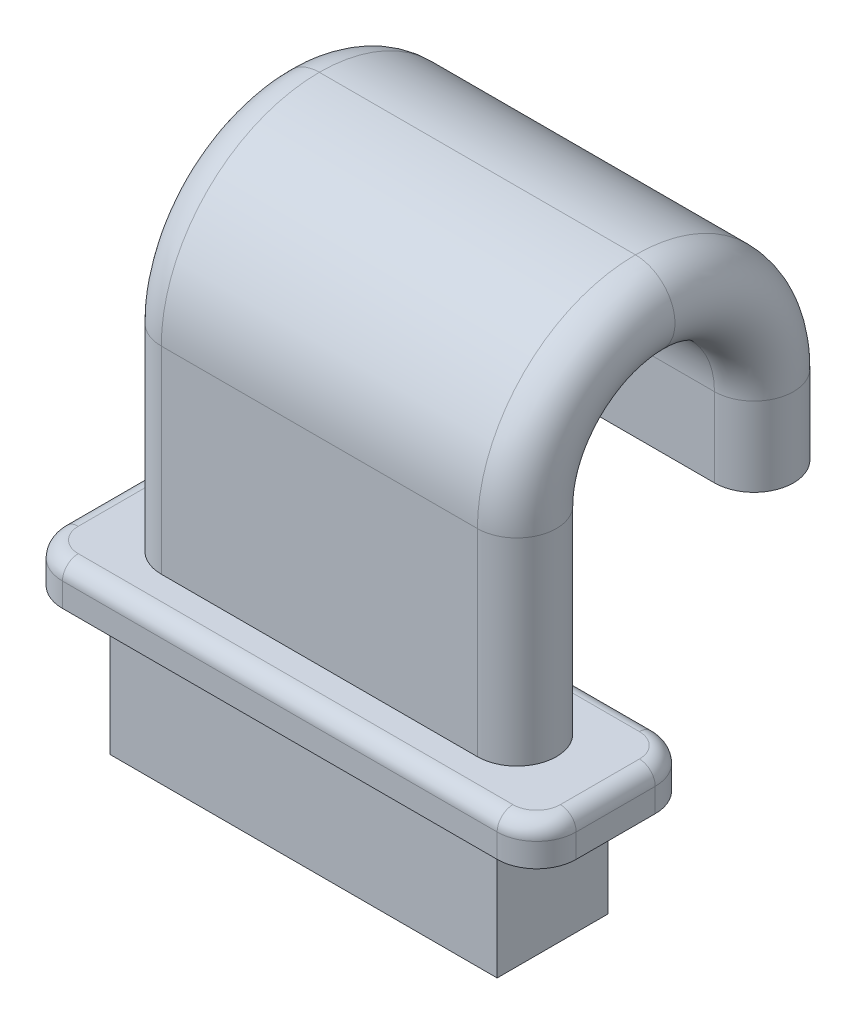
SolidWorks part; units mm, degrees
ref_plane "Front Plane" through (0, 0, 0) normal (0, 0, 1) x (1, 0, 0)
ref_plane "Top Plane" through (0, 0, 0) normal (0, 1, 0) x (1, 0, 0)
ref_plane "Right Plane" through (0, 0, 0) normal (1, 0, 0) x (0, 0, -1)
sketch "Sketch1" plane through (0, 0, 0) normal (1, 0, 0) x (0, 0, -1)
  line L0 (0, 0) -> (0, 25)
  line L2 (30, 25) -> (30, 15)
  arc A0 (0, 25) -> (15, 40) centre (15, 25) cw
  arc A1 (15, 40) -> (30, 25) centre (15, 25) cw
  point P2 (0, 0)
  point P8 (0, 40)
  point P11 (39.9467, 37.9361)
  point P12 (0, 0)
  point P13 (0, 0)
  point P14 (0, 0)
  point P15 (0, 0)
  point P16 (0, 0)
  dimension "D4" = 15
  dimension "D5" = 15
  dimension "D1" = 40
  dimension "D2" = 40
  dimension "D3" = 25
sketch "Sketch2" plane through (0, 0, 0) normal (0, 1, 0) x (1, 0, 0)
  line L0 (0, 0) -> (-40, 0) construction
  line L1 (0, -5) -> (-40, -5)
  line L2 (0, 5) -> (-40, 5)
  arc A1 (0, -5) -> (0, 5) centre (0, 0) ccw
  arc A2 (-40, 5) -> (-40, -5) centre (-40, 0) ccw
  point P2 (-20, 0)
  dimension "D1" = 5
  dimension "D2" = 40
sweep "Sweep1" add profiles "Sketch2" path "Sketch1"
sketch "Sketch3" plane through (0, 0, 0) normal (0, -1, 0) x (1, 0, 0)
  line L0 (5, 0) -> (-45, 0) construction
  line L1 (7.5, -10) -> (-47.5, -10)
  line L2 (12.5, -5) -> (12.5, 5)
  line L3 (7.5, 10) -> (-47.5, 10)
  line L4 (-52.5, -5) -> (-52.5, 5)
  line L5 (-20, -5) -> (-20, 5) construction
  line L6 (0, -5) -> (-40, -5) construction
  line L7 (-40, 5) -> (0, 5) construction
  arc A0 (0, -5) -> (0, 5) centre (0, 0) ccw construction
  arc A1 (-40, 5) -> (-40, -5) centre (-40, 0) ccw construction
  arc A2 (-47.5, -10) -> (-52.5, -5) centre (-47.5, -5) cw
  arc A3 (-47.5, 10) -> (-52.5, 5) centre (-47.5, 5) ccw
  arc A4 (12.5, 5) -> (7.5, 10) centre (7.5, 5) ccw
  arc A5 (7.5, -10) -> (12.5, -5) centre (7.5, -5) ccw
  point P18 (0, 0)
  point P19 (-20, -5)
  point P24 (-52.5, 10)
  point P27 (12.5, 10)
  dimension "D4" = 5
  dimension "D5" = 5
  dimension "D6" = 5
  dimension "D7" = 5
  dimension "D1" = 32.5
  dimension "D2" = 65
  dimension "D3" = 20
extrude "Boss-Extrude1" add sketch "Sketch3" along normal blind 5
fillet "Fillet1" radius 2 8 edges at (11.0355, 0, 8.5355) (12.5, 0, 0) (11.0355, 0, -8.5355) (-20, 0, -10) (-51.0355, 0, -8.5355) (-52.5, 0, 0) (-51.0355, 0, 8.5355) (-20, 0, 10)
sketch "Sketch4" plane through (0, -5, 0) normal (0, -1, 0) x (1, 0, 0)
  line L0 (12.5, -5) -> (12.5, 5) construction
  line L1 (-42.5, 5) -> (2.5, 5)
  line L2 (-42.5, 5) -> (-42.5, -5)
  line L3 (-42.5, -5) -> (2.5, -5)
  line L4 (2.5, 5) -> (2.5, -5)
  line L5 (-52.5, 5) -> (-52.5, -5) construction
  line L6 (7.5, 10) -> (-47.5, 10) construction
  line L7 (-47.5, -10) -> (7.5, -10) construction
  dimension "D1" = 10
  dimension "D2" = 10
  dimension "D3" = 5
  dimension "D4" = 5
extrude "Cut-Extrude4" cut sketch "Sketch4" against normal blind 3
shell "Shell2" thickness 1.5 removed face at (-20, 15, -30) removed face at (-20, -2, 0)
sketch "Sketch5" plane through (0, -5, 0) normal (0, -1, 0) x (1, 0, 0)
  line L0 (2.5, -5) -> (2.5, 5) construction
  line L1 (-42.5, 5) -> (-42.5, -5) construction
  line L2 (-42.5, -5) -> (2.5, -5) construction
  line L3 (2.5, 5) -> (-42.5, 5) construction
  line L4 (2.5, -5) -> (2.5, 5)
  line L5 (-42.5, 5) -> (-42.5, -5)
  line L6 (-42.5, -5) -> (2.5, -5)
  line L7 (2.5, 5) -> (-42.5, 5)
  line L8 (4.5, 7) -> (-44.5, 7)
  line L9 (-44.5, 7) -> (-44.5, -7)
  line L10 (-44.5, -7) -> (4.5, -7)
  line L11 (4.5, -7) -> (4.5, 7)
  dimension "D1" = 2
extrude "Boss-Extrude2" add sketch "Sketch5" along normal blind 16
